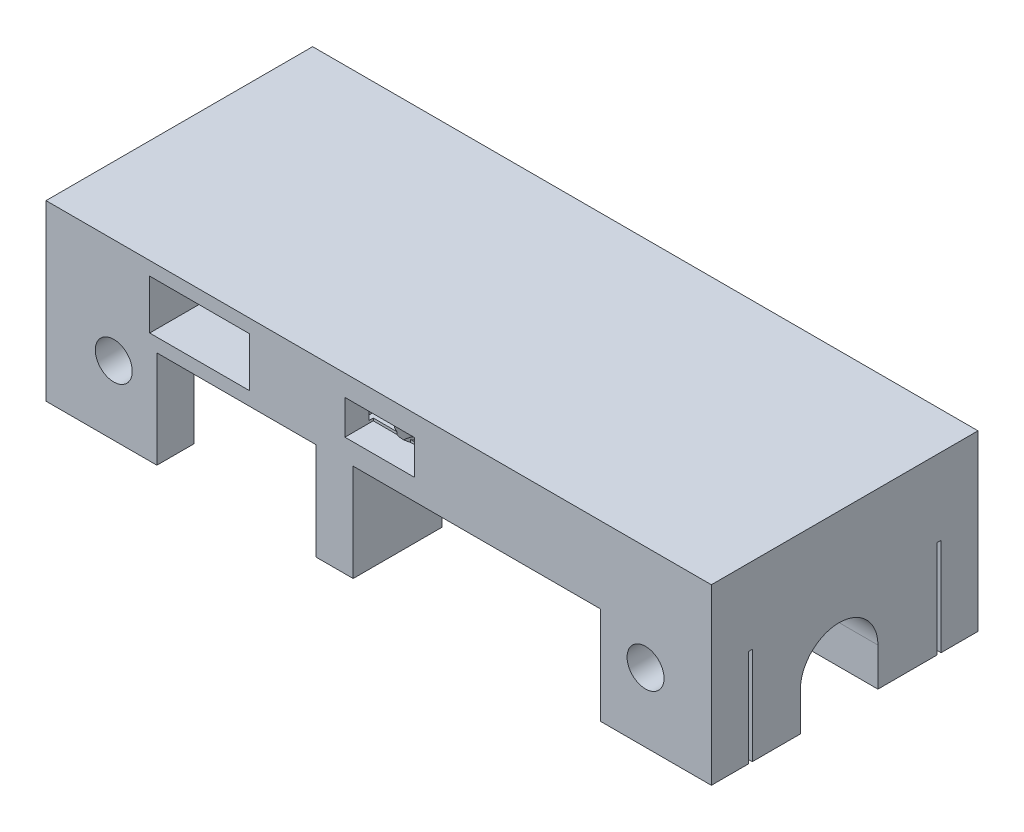
SolidWorks part; units mm, degrees
note: '?' marks a value the reader was unsure of.
ref_plane "Front Plane" through (0, 0, 0) normal (0, 0, 1) x (1, 0, 0)
ref_plane "Top Plane" through (0, 0, 0) normal (0, 1, 0) x (1, 0, 0)
ref_plane "Right Plane" through (0, 0, 0) normal (1, 0, 0) x (0, 0, -1)
sketch "Sketch2" plane through (10.5283, 2.7166, 0) normal (0, 0, 1) x (1, 0, 0)
  line L0 (-37.5283, 0.3834) -> (16.4717, 0.3834)
  line L1 (16.4717, 0.3834) -> (16.4717, -5.8166)
  line L2 (16.4717, -5.8166) -> (-37.5283, -5.8166)
  line L3 (-37.5283, -5.8166) -> (-37.5283, 0.3834)
  point P6 (-10.5283, 0.3834)
  point P7 (16.4717, -2.7166)
  dimension "D1" = 6.2
  dimension "D2" = 54
extrude "Boss-Extrude2" add sketch "Sketch2" along normal mid plane 25
sketch "Sketch3" plane through (0, -3.1, 0) normal (0, -1, 0) x (1, 0, 0)
  circle A0 centre (-12.166, -142.3748) radius 2.8
  dimension "D1" = 5.6
extrude "Cut-Extrude1" cut sketch "Sketch3" against normal up to surface (6.2 mm away)
ref_plane "Plane1" through (0, 0, 0) normal (0, 1, 0) x (1, 0, 0)
sketch "Sketch4" plane through (0, 0, 0) normal (0, 1, 0) x (1, 0, 0)
  line L1 (-10.6351, 0.6607) -> (-14.5351, 2.9124)
  line L2 (-14.5351, 2.9124) -> (-18.4351, 0.6607)
  line L3 (-18.4351, 0.6607) -> (-18.4351, -3.8426)
  line L4 (-18.4351, -3.8426) -> (-14.5351, -6.0943)
  line L5 (-14.5351, -6.0943) -> (-10.6351, -3.8426)
  line L6 (-10.6351, -3.8426) -> (-10.6351, 0.6607)
  circle A0 centre (-14.5351, -1.5909) radius 3.9 construction
  circle A1 centre (-14.5351, -1.5909) radius 2.8 construction
  dimension "D1" = 7.8
extrude "Cut-Extrude2" cut sketch "Sketch4" against normal mid plane 3.8
sketch "Sketch6" plane through (0, 0, 12.5) normal (0, 0, 1) x (1, 0, 0)
  line L0 (27, 3.1) -> (-27, 3.1) construction
  line L1 (-18.5851, -2) -> (-10.4851, -2)
  line L2 (-18.5851, -2) -> (-18.5851, 2)
  line L3 (-18.5851, 2) -> (-10.4851, 2)
  line L4 (-10.4851, -2) -> (-10.4851, 2)
  line L5 (-27, -3.1) -> (27, -3.1) construction
  line L6 (-10.6351, -1.9) -> (-10.6351, 1.9) construction
  line L7 (-18.4351, -1.9) -> (-18.4351, 1.9) construction
  dimension "D1" = 1.1
  dimension "D2" = 1.1
  dimension "D3" = 0.15
  dimension "D4" = 0.15
extrude "Cut-Extrude3" cut sketch "Sketch6" against normal up to vertex (8.6574 mm away) up to point (-18.4351, 1.9, 3.8426)
sketch "Sketch7" plane through (0, -3.1, 0) normal (0, -1, 0) x (1, 0, 0)
  line L0 (-27, -12.5) -> (27, -12.5) construction
  line L1 (-27, 12.5) -> (-24, 12.5)
  line L2 (-27, 12.5) -> (-27, -12.5)
  line L3 (-27, -12.5) -> (-24, -12.5)
  line L4 (-24, 12.5) -> (-24, -12.5)
  dimension "D1" = 3
extrude "Boss-Extrude3" add sketch "Sketch7" along normal offset from surface (7.9 mm away) 2
sketch "Sketch8" plane through (-27, 0, 0) normal (-1, 0, 0) x (0, 0, 1)
  line L1 (-12.5, -11) -> (12.5, -11) construction
  line L3 (4.7409, -11) -> (-1.5591, -11) construction
  line L4 (-0.6607, -1.9) -> (3.8426, -1.9) construction
  line L5 (-1.5591, -7.9) -> (-1.5591, -11)
  line L6 (-1.5591, -11) -> (4.7409, -11)
  line L7 (4.7409, -11) -> (4.7409, -7.9)
  arc A0 (-1.5591, -7.9) -> (4.7409, -7.9) centre (1.5909, -7.9) cw
  point P9 (1.5909, -1.9)
  dimension "D1" = 3.15
  dimension "D2" = 3.1
extrude "Cut-Extrude4" cut sketch "Sketch8" against normal blind 2
sketch "Sketch9" plane through (-24, 0, 0) normal (1, 0, 0) x (0, 0, -1)
  line L17 (151.7748, -8.8) -> (132.9748, -8.8) construction
  circle A0 centre (142.3748, -8.1) radius 0.7
  dimension "D1" = 1.4
extrude "Cut-Extrude5" cut sketch "Sketch9" against normal blind 2
sketch "Sketch13" plane through (0, 3.1, 0) normal (0, 1, 0) x (1, 0, 0)
  line L0 (-27, 9.68) -> (27, 9.68)
  line L1 (-27, -12.5) -> (-27, 12.5) construction
  line L2 (27, -12.5) -> (27, 12.5) construction
  line L3 (27, 12.5) -> (-27, 12.5) construction
  line L4 (-27, 9.68) -> (-27, 12.5)
  line L5 (-27, 12.5) -> (27, 12.5)
  line L6 (27, 12.5) -> (27, 9.68)
  dimension "D1" = 2.82
extrude "Cut-Extrude6" cut sketch "Sketch13" against normal through all
sketch "Sketch14" plane through (27, 0, 0) normal (1, 0, 0) x (0, 0, -1)
  line L0 (8.25, 7.6) -> (9.68, -11)
  line L1 (9.68, -11) -> (8.25, -11)
  line L3 (8.25, -11) -> (8.25, 7.6)
  line L4 (-1.41, 3.1) -> (-1.41, -1.8305) construction
  line L5 (-12.5, 3.1) -> (9.68, 3.1) construction
  line L6 (-11.07, -11) -> (-11.07, 7.6)
  line L7 (-12.5, -11) -> (-11.07, -11)
  line L8 (-11.07, 7.6) -> (-12.5, -11)
  dimension "D1" = 18.6
  dimension "D2" = 1.43
sketch "Sketch16" plane through (-27, 0, 0) normal (-1, 0, 0) x (0, 0, 1)
  line L1 (4.7409, -11) -> (12.5, -11) construction
  circle A0 centre (1.41, -47.6) radius 36.6
  dimension "D1" = 73.2
ref_axis "Axis1" through (-14.5351, -1.9, 1.5909) along (0, -1, 0)?
ref_plane "Plane2" through (-14.5351, 0, 0) normal (-1, 0, 0) x (0, 0, 1)
mirror "Mirror1" about plane through (-14.5351, 0, 0) normal (-1, 0, 0) of "Boss-Extrude3", "Cut-Extrude4", "Cut-Extrude5"
sketch "Sketch15" plane through (27, 0, 0) normal (1, 0, 0) x (0, 0, -1)
  line L2 (8.2488, 7.5999) -> (9.68, -11)
  line L3 (-11.07, 7.6) -> (-12.5, -11)
  line L12 (-11.07, 7.6) -> (-17.5, -11)
  line L13 (-17.5, -11) -> (-12.5, -11)
  line L14 (8.2488, 7.5999) -> (14.68, -11)
  line L15 (14.68, -11) -> (9.68, -11)
  line M7 (-12.5, -3.1) -> (9.68, -3.1)
  line M8 (9.68, -3.1) -> (9.68, 3.1)
  line M9 (9.68, 3.1) -> (-12.5, 3.1)
  line M10 (-12.5, 3.1) -> (-12.5, -3.1)
  dimension "D2" = 5
  dimension "D3" = 5
  dimension "D1" = 94.4
  dimension "D4" = 1.4312
  dimension "D5" = 22.18
  dimension "D6" = 1.43
  dimension "D7" = 94.396
extrude "Cut-Extrude7" [suppressed] cut sketch "Sketch15" against normal through all contours L12 L13 L3 M7 M10 M9 | L15 L14 L2 M9 M8 M7 | L3 M9 M10 M7 | L2 M9 M7 M8
sketch "Sketch17" plane through (-2.0702, 0, 0) normal (1, 0, 0) x (0, 0, -1)
  line L3 (-4.7409, -11) -> (1.5591, -11)
  line L4 (1.5591, -11) -> (1.5591, -7.9)
  line L5 (-4.7409, -7.9) -> (-4.7409, -11)
  line L6 (-4.7409, -11) -> (1.5591, -11)
  line L7 (1.5591, -11) -> (1.5591, -7.9)
  line L8 (-4.7409, -7.9) -> (-4.7409, -11)
  arc A1 (1.5591, -7.9) -> (-4.7409, -7.9) centre (-1.5909, -7.9) ccw
  arc A2 (1.5591, -7.9) -> (-4.7409, -7.9) centre (-1.5909, -7.9) ccw
  dimension "D1" = 0
extrude "Cut-Extrude8" [suppressed] cut sketch "Sketch17" along normal up to surface (28.72 mm away)
sketch "Sketch18" plane through (0, -3.1, 0) normal (0, 1, 0) x (1, 0, 0)
  line L4 (-5.0702, 12.5) -> (-5.0702, 9.68)
  line L5 (-5.0702, 9.68) -> (-2.0702, 9.68)
  line L6 (-2.0702, 9.68) -> (-2.0702, 12.5)
  line L7 (-2.0702, 12.5) -> (-5.0702, 12.5)
  line L8 (-5.0702, 12.5) -> (-5.0702, 9.68)
  line L9 (-5.0702, 9.68) -> (-2.0702, 9.68)
  line L10 (-2.0702, 9.68) -> (-2.0702, 12.5)
  line L11 (-2.0702, 12.5) -> (-5.0702, 12.5)
  dimension "D1" = 0
extrude "Cut-Extrude9" cut sketch "Sketch18" against normal blind 10
sketch "Sketch19" plane through (-27, 0, 0) normal (-1, 0, 0) x (0, 0, 1)
  line L0 (1.5909, -8.1) -> (1.5909, -0.9391) construction
  line L1 (12.5, 3.1) -> (-9.68, 3.1) construction
  line L2 (11.9609, 3.1) -> (12.5, 3.1)
  line L3 (11.9609, 3.1) -> (11.9609, -11)
  line L4 (11.9609, -11) -> (12.5, -11)
  line L5 (12.5, 3.1) -> (12.5, -11)
  line L6 (4.7409, -11) -> (4.7409, -7.9) construction
  dimension "D1" = 7.22
extrude "Cut-Extrude11" cut sketch "Sketch19" against normal through all contours L5 L4 L3 L2
sketch "Sketch20" plane through (27, 0, 0) normal (1, 0, 0) x (0, 0, -1)
  line L0 (9.6637, 3.2923) -> (9.7533, 2.2334)
  line L1 (10.7539, -9.6) -> (9.0204, 10.9) construction
  line L2 (9.7533, 2.2334) -> (9.8296, 3.2923)
  line L3 (9.8296, 3.2923) -> (9.6637, 3.2923)
  line L4 (-1.5909, -8.1) -> (-1.5909, 2.0673) construction
  line L5 (-13.0114, 3.2923) -> (-12.8456, 3.2923)
  line L6 (-12.9351, 2.2334) -> (-13.0114, 3.2923)
  line L7 (-12.8456, 3.2923) -> (-12.9351, 2.2334)
extrude "Cut-Extrude12" [suppressed] cut sketch "Sketch20" against normal through all
sketch "Sketch21" [suppressed] plane through (27, 0, 0) normal (1, 0, 0) x (0, 0, -1)
  line L0 (-10.8998, 3) -> (-11.8756, -9.7)
  line L1 (-11.8756, -9.7) -> (-10.9596, -9.7)
  line L2 (-10.9596, -9.7) -> (-10.8998, 3)
  line L3 (-0.6396, -6.9) -> (-0.6396, -2.1136) construction
  line L4 (9.6804, -9.7) -> (9.6206, 3)
  line L5 (10.5965, -9.7) -> (9.6804, -9.7)
  line L6 (9.6206, 3) -> (10.5965, -9.7)
  line L7 (-10.928, -3) -> (-11.3608, -3)
  line L8 (-10.9596, -3) -> (9.68, -3) construction
  line L9 (9.6489, -3) -> (10.0817, -3)
sketch "Sketch22" plane through (0, -3.1, 0) normal (0, -1, 0) x (1, 0, 0)
  line L1 (15, 10.4728) -> (12.15, 8.8273)
  line L2 (12.15, 8.8273) -> (12.15, 5.5364)
  line L3 (12.15, 5.5364) -> (15, 3.891)
  line L4 (15, 3.891) -> (17.85, 5.5364)
  line L5 (17.85, 5.5364) -> (17.85, 8.8273)
  line L6 (17.85, 8.8273) -> (15, 10.4728)
  line L7 (15, -2.5847) -> (12.15, -4.2301)
  line L8 (12.15, -4.2301) -> (12.15, -7.521)
  line L9 (12.15, -7.521) -> (15, -9.1665)
  line L10 (15, -9.1665) -> (17.85, -7.521)
  line L11 (17.85, -7.521) -> (17.85, -4.2301)
  line L12 (17.85, -4.2301) -> (15, -2.5847)
  circle A0 centre (15, 7.1819) radius 1.55 construction
  circle A2 centre (15, 7.1819) radius 1.55 construction
  circle A3 centre (15, -5.8756) radius 1.55 construction
  circle A4 centre (15, 7.1819) radius 2.85 construction
  circle A5 centre (15, -5.8756) radius 2.85 construction
  circle A6 centre (15, -5.8756) radius 1.55 construction
  dimension "D1" = 5.7
extrude "Cut-Extrude13" cut sketch "Sketch22" against normal blind 2.5
sketch "Sketch23" plane through (0, 3.1, 0) normal (0, 1, 0) x (1, 0, 0)
  line L0 (27, -11.9609) -> (-27, -11.9609) construction
  line L1 (-2.0702, -4.7409) -> (-2.0702, -11.9609) construction
  line L2 (-12.166, 142.3748) -> (-5.8584, 142.3748) construction
  circle A0 centre (-0.2702, -8.1609) radius 1.6
  circle A1 centre (-0.2702, 292.9104) radius 1.6
  dimension "D1" = 3.2
  dimension "D2" = 3.8
  dimension "D3" = 1.8
extrude "Cut-Extrude15" cut sketch "Sketch23" against normal blind 7 from offset 2 contours A1 | A0 offset against normal yes
sketch "Sketch24" plane through (0, 0, 0) normal (0, 1, 0) x (1, 0, 0)
  line L1 (-0.2702, -11.4518) -> (2.5798, -9.8064)
  line L2 (2.5798, -9.8064) -> (2.5798, -6.5155)
  line L3 (2.5798, -6.5155) -> (-0.2702, -4.87)
  line L4 (-0.2702, -4.87) -> (-3.1202, -6.5155)
  line L5 (-3.1202, -6.5155) -> (-3.1202, -9.8064)
  line L6 (-3.1202, -9.8064) -> (-0.2702, -11.4518)
  line L7 (-0.2702, 1.6882) -> (2.5798, 3.3336)
  line L8 (2.5798, 3.3336) -> (2.5798, 6.6245)
  line L9 (2.5798, 6.6245) -> (-0.2702, 8.27)
  line L10 (-0.2702, 8.27) -> (-3.1202, 6.6245)
  line L11 (-3.1202, 6.6245) -> (-3.1202, 3.3336)
  line L12 (-3.1202, 3.3336) -> (-0.2702, 1.6882)
  circle A0 centre (-0.2702, -8.1609) radius 2.85 construction
  circle A1 centre (-0.2702, 4.9791) radius 2.85 construction
  dimension "D1" = 5.7
extrude "Cut-Extrude16" cut sketch "Sketch24" against normal mid plane 2.4
sketch "Sketch26" plane through (0, 0, 11.9609) normal (0, 0, 1) x (1, 0, 0)
  line L1 (-2.74, -1.4) -> (2.9, -1.4)
  line L2 (-2.74, -1.4) -> (-2.74, 1.4)
  line L3 (-2.74, 1.4) -> (2.9, 1.4)
  line L4 (2.9, -1.4) -> (2.9, 1.4)
  line L5 (2.5798, 1.2) -> (-0.2702, 1.2) construction
  line L6 (2.5798, -1.2) -> (-0.2702, -1.2) construction
  dimension "D1" = 0.2
  dimension "D2" = 0.2
  dimension "D3" = 2.9
  dimension "D4" = 2.74
extrude "Cut-Extrude17" cut sketch "Sketch26" against normal blind 2.3
sketch "Sketch28" plane through (0, -3.1, 0) normal (0, -1, 0) x (1, 0, 0)
  line L0 (-14.5351, 1.5909) -> (13.1005, 1.5909) construction
ref_plane "Plane3" through (0, 0, 1.1405) normal (0, 0, -1) x (-1, 0, 0)
mirror "Mirror4" about plane through (0, 0, 1.1405) normal (0, 0, -1) of "Cut-Extrude17"
sketch "Sketch29" plane through (0, -3.1, 0) normal (0, -1, 0) x (1, 0, 0)
  line L1 (27, 11.9609) -> (18, 11.9609)
  line L2 (27, 11.9609) -> (27, 8.9609)
  line L3 (27, 8.9609) -> (18, 8.9609)
  line L4 (18, 11.9609) -> (18, 8.9609)
  line L5 (-27, 11.9609) -> (-18, 11.9609)
  line L6 (-27, 11.9609) -> (-27, 8.9609)
  line L7 (-27, 8.9609) -> (-18, 8.9609)
  line L8 (-18, 11.9609) -> (-18, 8.9609)
  dimension "D1" = 3
  dimension "D4" = 9
extrude "Boss-Extrude5" add sketch "Sketch29" along normal up to surface (7.9 mm away) up to face at (-25.75, -11, 1.3657)
mirror "Mirror5" about plane through (0, 0, 1.1405) normal (0, 0, -1) of "Boss-Extrude5"
sketch "Sketch34" plane through (0, 0, 1.1405) normal (0, 0, -1) x (-1, 0, 0)
  line L4 (-27, -3.1) -> (-27, -11)
  line L5 (-27, -11) -> (-18, -11)
  line L6 (-18, -11) -> (-18, -3.1)
  line L7 (-18, -3.1) -> (-27, -3.1)
  line L8 (-27, -3.1) -> (-27, -11)
  line L9 (-27, -11) -> (-18, -11)
  line L10 (-18, -11) -> (-18, -3.1)
  line L11 (-18, -3.1) -> (-27, -3.1)
  dimension "D1" = 0
extrude "Boss-Extrude6" add sketch "Sketch34" along normal mid plane 15
sketch "Sketch35" plane through (27, 0, 0) normal (1, 0, 0) x (0, 0, -1)
  line L3 (-4.7409, -11) -> (1.5591, -11)
  line L4 (1.5591, -11) -> (1.5591, -7.9)
  line L5 (-4.7409, -7.9) -> (-4.7409, -11)
  line L6 (-4.7409, -11) -> (1.5591, -11)
  line L7 (1.5591, -11) -> (1.5591, -7.9)
  line L8 (-4.7409, -7.9) -> (-4.7409, -11)
  arc A1 (1.5591, -7.9) -> (-4.7409, -7.9) centre (-1.5909, -7.9) ccw
  arc A2 (1.5591, -7.9) -> (-4.7409, -7.9) centre (-1.5909, -7.9) ccw
  dimension "D1" = 0
extrude "Cut-Extrude19" cut sketch "Sketch35" against normal up to surface (9 mm away) up to face at (18, -7.05, 10.4609)
sketch "Sketch36" plane through (0, -11, 0) normal (0, -1, 0) x (1, 0, 0)
  line L0 (-18, -9.68) -> (-18, -6.68) construction
  line L1 (-18, 11.9609) -> (-18, 8.9609) construction
  line L2 (-18, -150.4966) -> (-18, -147.4966)
  line L3 (-20.7547, -137.2529) -> (-18, -137.2529)
  line L4 (-20.7547, -147.4966) -> (-18, -147.4966)
  line L5 (-18, -137.2529) -> (-18, -134.2529)
  arc A0 (-18, -150.4966) -> (-20.7547, -147.4966) centre (-12.166, -142.3748) cw
  arc A1 (-20.7547, -137.2529) -> (-18, -134.2529) centre (-12.166, -142.3748) cw
  dimension "D1" = 10
  dimension "D2" = 3
extrude "Cut-Extrude20" cut sketch "Sketch36" against normal blind 2.5
sketch "Sketch37" plane through (0, -3.1, 0) normal (0, -1, 0) x (1, 0, 0)
  line L0 (-18, 8.9609) -> (-18, 11.9609) construction
  line L1 (-24, 11.4609) -> (-18, 11.4609)
  line L2 (-24, 11.4609) -> (-24, 5.4609)
  line L3 (-24, 5.4609) -> (-18, 5.4609)
  line L4 (-18, 11.4609) -> (-18, 5.4609)
  line L5 (-12.166, -142.3748) -> (-20.2872, -142.3748) construction
  line L6 (-18, -296.2104) -> (-18, -290.2104)
  line L7 (-24, -290.2104) -> (-18, -290.2104)
  line L8 (-24, -296.2104) -> (-24, -290.2104)
  line L9 (-24, -296.2104) -> (-18, -296.2104)
  line L10 (-18, 11.9609) -> (-27, 11.9609) construction
  dimension "D1" = 6
  dimension "D2" = 6.5
extrude "Boss-Extrude7" [suppressed] add sketch "Sketch37" along normal up to surface (3.7 mm away)
sketch "Sketch31" plane through (0, 0, -9.68) normal (0, 0, -1) x (-1, 0, 0)
  circle A0 centre (-21.66, -5.4) radius 1.5
  circle A1 centre (21.5, -5.4) radius 1.5
  dimension "D1" = 3
extrude "Cut-Extrude18" cut sketch "Sketch31" against normal through all
